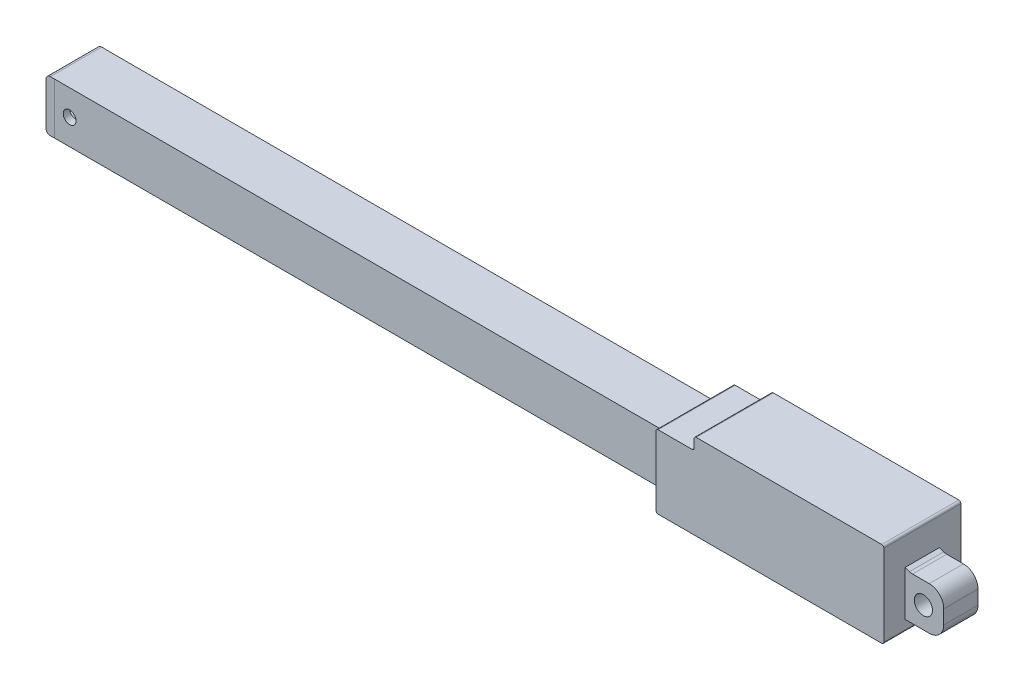
SolidWorks part; units mm, degrees
ref_plane "Front Plane" through (0, 0, 0) normal (0, 0, 1) x (1, 0, 0)
ref_plane "Top Plane" through (0, 0, 0) normal (0, 1, 0) x (1, 0, 0)
ref_plane "Right Plane" through (0, 0, 0) normal (1, 0, 0) x (0, 0, -1)
sketch "Sketch2" plane through (0, 0, 0) normal (0, 0, 1) x (1, 0, 0)
  line L0 (145.4775, 11.945) -> (145.4775, 14.0125)
  line L1 (1, 0) -> (145.4775, 0)
  line L2 (0, 1) -> (0, 10.945)
  line L3 (1, 11.945) -> (145.4775, 11.945)
  line L4 (145.4775, 0) -> (145.4775, 11.945)
  line L5 (145.4775, 0) -> (145.4775, -2.0675)
  line L6 (145.9775, -2.5675) -> (198.1775, -2.5675)
  line L7 (198.6775, 0) -> (198.6775, -2.0675)
  line L8 (198.1775, 17.4225) -> (154.8775, 17.4225)
  line L9 (154.3775, 16.9225) -> (154.3775, 15.0125)
  line L10 (153.8775, 14.5125) -> (145.9775, 14.5125)
  line L11 (198.6775, 0) -> (204.2883, 0)
  line L12 (207.6775, 3.3892) -> (207.6775, 6.6533)
  line L13 (204.2883, 10.0425) -> (200.3774, 10.0425)
  line L14 (199.6775, 10.169) -> (198.6775, 10.5425)
  line L15 (202.9275, 0) -> (202.9275, 10.0425) construction
  line L16 (2, 11.945) -> (2, 0)
  line L17 (198.6775, 10.5425) -> (198.6775, 16.9225)
  line L18 (2, 5.9725) -> (4, 5.9725) construction
  line L19 (0, 5.9725) -> (2, 5.9725) construction
  arc A0 (0, 10.945) -> (1, 11.945) centre (1, 10.945) cw
  arc A1 (1, 0) -> (0, 1) centre (1, 1) cw
  arc A2 (154.8775, 17.4225) -> (154.3775, 16.9225) centre (154.8775, 16.9225) ccw
  arc A3 (198.6775, 16.9225) -> (198.1775, 17.4225) centre (198.1775, 16.9225) ccw
  arc A4 (198.1775, -2.5675) -> (198.6775, -2.0675) centre (198.1775, -2.0675) ccw
  arc A5 (145.4775, -2.0675) -> (145.9775, -2.5675) centre (145.9775, -2.0675) ccw
  arc A6 (145.4775, 14.0125) -> (145.9775, 14.5125) centre (145.9775, 14.0125) cw
  arc A7 (154.3775, 15.0125) -> (153.8775, 14.5125) centre (153.8775, 15.0125) cw
  arc A8 (204.2883, 0) -> (207.6775, 3.3892) centre (204.2883, 3.3892) ccw
  arc A9 (207.6775, 6.6533) -> (204.2883, 10.0425) centre (204.2883, 6.6533) ccw
  circle A10 centre (202.9275, 5.0213) radius 2.125
  arc A11 (200.3774, 10.0425) -> (199.6775, 10.169) centre (200.3774, 12.0425) cw
  circle A12 centre (5.5, 5.9725) radius 1.5
  point P7 (0, 11.945)
  point P10 (0, 0)
  point P23 (191, -2.5)
  point P26 (145.4775, -2.5675)
  point P29 (145.4775, 14.5125)
  point P32 (154.3775, 14.5125)
  point P44 (202.9275, 5.0213)
  point P54 (4, 5.9725)
  dimension "D3" = 1
  dimension "D8" = 0.5
  dimension "D12" = 4.25
  dimension "D13" = 2
  dimension "D14" = 3
  dimension "D9" = 4.25
  dimension "D1" = 145.4775
  dimension "D2" = 11.945
  dimension "D4" = 53.2
  dimension "D5" = 17.08
  dimension "D6" = 19.99
  dimension "D7" = 44.3
  dimension "D10" = 10.0425
  dimension "D11" = 9
  dimension "D15" = 2
  dimension "D16" = 1
  dimension "D17" = 0.5
extrude "Boss-Extrude1" add sketch "Sketch2" along normal mid plane 18 contours L9 A7 L10 A6 L0 L4 L5 A5 L6 A4 A3 L8 A2 region at (174.5883, 7.0743, 0)
extrude "Boss-Extrude2" add sketch "Sketch2<3>" along normal mid plane 11.95 contours L3 L16 L1 L4 A12 region at (74.0214, 5.9725, 0)
sketch "Sketch2<3>" plane through (0, 0, 0) normal (0, 0, 1) x (1, 0, 0) same geometry as "Sketch2"
extrude "Boss-Extrude3" add sketch "Sketch2<4>" along normal mid plane 12 contours A1 L1 L16 L3 A0 L2 region at (1.0142, 5.9725, 0)
sketch "Sketch2<4>" plane through (0, 0, 0) normal (0, 0, 1) x (1, 0, 0) same geometry as "Sketch2"
sketch "Sketch7" plane through (0, 0, 0) normal (-1, 0, 0) x (0, 0, 1)
  line L0 (0, 1) -> (6, 5.9725) construction
  line L1 (6, 1) -> (-6, 1) construction
  line L2 (6, 1) -> (6, 10.945) construction
  line L3 (6, 5.9725) -> (0, 5.9725) construction
  circle A0 centre (0, 5.9725) radius 4.45
  dimension "D1" = 8.9
extrude "Cut-Extrude4" cut sketch "Sketch7" against normal blind 138
sketch "Sketch8" plane through (0, 0, 9) normal (0, 0, 1) x (1, 0, 0)
  line L0 (198.6775, 10.5425) -> (211.4521, 15.9059)
  line L1 (211.4521, 15.9059) -> (207.0125, -2.0597)
  line L2 (207.0125, -2.0597) -> (198.6775, 0)
  line L3 (198.6775, 0) -> (204.2883, 0) construction
  line L4 (198.6775, 0) -> (198.6775, 10.5425)
extrude "Cut-Extrude6" cut sketch "Sketch8" against normal mid plane 10
sketch "Sketch10" plane through (0, 0, -9) normal (0, 0, -1) x (-1, 0, 0)
  line L0 (-198.6775, 10.5425) -> (-218.6867, 39.1128)
  line L1 (-218.6867, 39.1128) -> (-201.4433, -35.5929)
  line L2 (-201.4433, -35.5929) -> (-198.6775, 0)
  line L3 (-198.6775, 0) -> (-198.6775, 10.5425)
extrude "Cut-Extrude7" cut sketch "Sketch10" against normal mid plane 10
